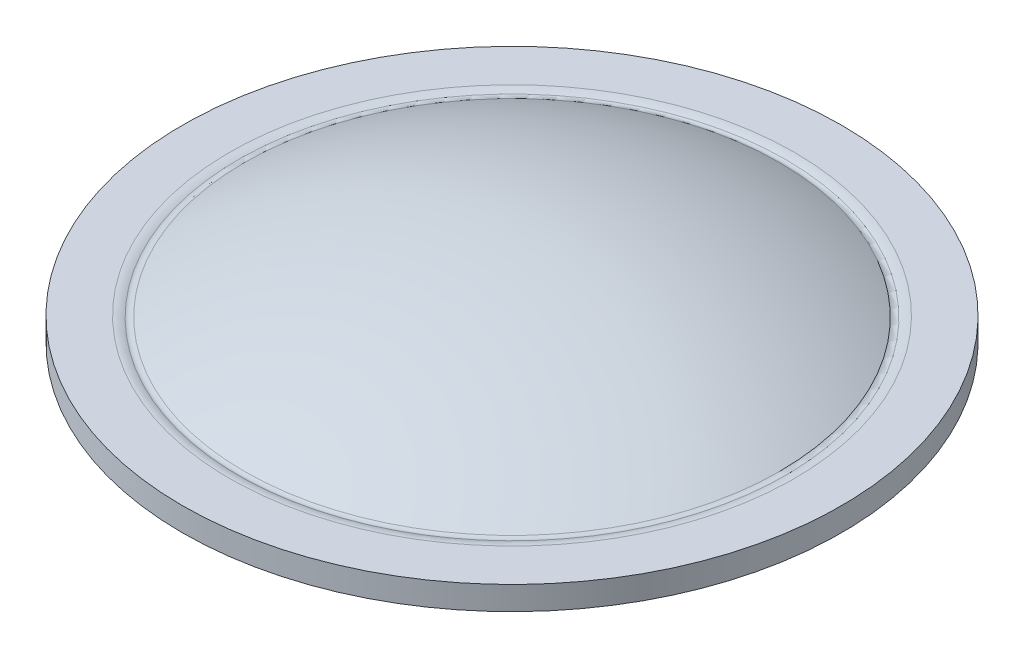
SolidWorks part; units mm, degrees
ref_plane "Спереди" through (0, 0, 0) normal (0, 0, 1) x (1, 0, 0)
ref_plane "Сверху" through (0, 0, 0) normal (0, 1, 0) x (1, 0, 0)
ref_plane "Справа" through (0, 0, 0) normal (1, 0, 0) x (0, 0, -1)
sketch "Эскиз1" plane through (0, 0, 0) normal (0, 0, 1) x (1, 0, 0)
  line L0 (-12, -2.866) -> (-14, -2.866)
  line L1 (-14, -2.866) -> (-14, -3.866)
  line L2 (-14, -3.866) -> (0, -3.866)
  line L3 (0, -3.866) -> (0, 0)
  arc A0 (0, 0) -> (-11.5, -3) centre (0, -23.5417) ccw
  arc A1 (-12, -2.866) -> (-11.5, -3) centre (-12, -3.866) cw
  dimension "D4" = 1
  dimension "D1" = 11.5
  dimension "D2" = 3
  dimension "D3" = 2
  dimension "D5" = 1
  dimension "D6" = 14
revolve "Повернуть1" add sketch "Эскиз1" angle 360 about L3
shell "Оболочка1" thickness 1 removed face at (0, -3.866, -14)
fillet "Скругление1" radius 0.3 1 edges at (0, -3, -11.5)
